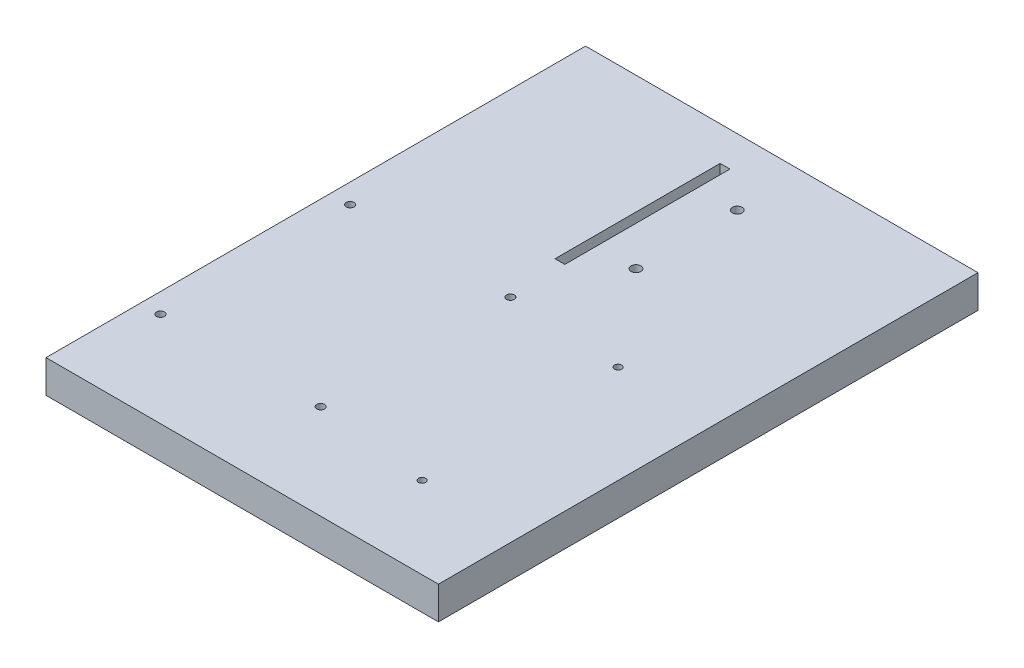
SolidWorks part; units mm, degrees
ref_plane "Front Plane" through (0, 0, 0) normal (0, 0, 1) x (1, 0, 0)
ref_plane "Top Plane" through (0, 0, 0) normal (0, 1, 0) x (1, 0, 0)
ref_plane "Right Plane" through (0, 0, 0) normal (1, 0, 0) x (0, 0, -1)
sketch "Sketch1" plane through (0, 0, 0) normal (0, 1, 0) x (1, 0, 0)
  line L1 (0, 0) -> (120, 0)
  line L2 (0, 0) -> (0, 165)
  line L3 (0, 165) -> (120, 165)
  line L4 (120, 0) -> (120, 165)
  dimension "D1" = 120
  dimension "D2" = 165
extrude "Base" add sketch "Sketch1" along normal blind 10
hole_wizard "Pi-MountHoles" positions "Sketch13" profile "Sketch14" counterbore size "M2" standard "ANSI Metric" end condition up to next
sketch "Sketch13" plane through (0, 0, 0) normal (0, -1, 0) x (-1, 0, 0)
  line L1 (0, 0) -> (-120, 0) construction
  line L2 (0, 165) -> (0, 0) construction
  point P0 (-6, 29)
  point P2 (-55, 29)
  point P4 (-55, 87)
  point P6 (-6, 87)
  dimension "D1" = 49
  dimension "D2" = 58
  dimension "D3" = 87
  dimension "D4" = 6
sketch "Sketch14" plane through (6, 0, -29) normal (1, 0, 0) x (0, 0, -1)
  line L0 (0, 0) -> (0, 10)
  line L1 (0, 10) -> (1.2, 10)
  line L3 (1.2, 10) -> (1.2, 1.6)
  line L4 (2.5, 1.6) -> (1.2, 1.6)
  line L5 (2.5, 1.6) -> (2.5, 0.025)
  line L6 (2.5, 0.025) -> (2.525, 0)
  line L7 (2.525, 0) -> (0, 0)
  line L8 (-2.5, 0.025) -> (-2.525, 0) construction
  line L11 (0, -6.35) -> (0, 107.95) construction
  dimension "Thru Hole Dia." = 2.4
  dimension "Thru Hole Depth" = 10
  dimension "C'Bore Dia." = 5
  dimension "C'Bore Depth" = 1.6
  dimension "Near C'Sink Dia." = 5.05
  dimension "Near C'Sink Angle" = 90
hole_wizard "Battery-MountHoles" positions "Sketch15" profile "Sketch16" counterbore size "M2" standard "ANSI Metric" end condition up to next
sketch "Sketch15" plane through (0, 0, 0) normal (0, -1, 0) x (-1, 0, 0)
  line L0 (0, 0) -> (-120, 0) construction
  circle A0 centre (-55, 87) radius 1.2 construction
  point P0 (-90, 25)
  point P2 (-90, 84.95)
  dimension "D1" = 59.95
  dimension "D2" = 25
  dimension "D3" = 35
sketch "Sketch16" plane through (90, 0, -25) normal (1, 0, 0) x (0, 0, -1)
  line L0 (0, 0) -> (0, 10)
  line L1 (0, 10) -> (1.1, 10)
  line L3 (1.1, 10) -> (1.1, 1.6)
  line L4 (2.5, 1.6) -> (1.1, 1.6)
  line L5 (2.5, 1.6) -> (2.5, 0.025)
  line L6 (2.5, 0.025) -> (2.525, 0)
  line L7 (2.525, 0) -> (0, 0)
  line L8 (-2.5, 0.025) -> (-2.525, 0) construction
  line L11 (0, -6.35) -> (0, 107.95) construction
  dimension "Thru Hole Dia." = 2.2
  dimension "Thru Hole Depth" = 10
  dimension "C'Bore Dia." = 5
  dimension "C'Bore Depth" = 1.6
  dimension "Near C'Sink Dia." = 5.05
  dimension "Near C'Sink Angle" = 90
sketch "Sketch17" plane through (0, 10, 0) normal (0, 1, 0) x (1, 0, 0)
  line L1 (51.65, 154.5) -> (54.65, 154.5)
  line L2 (51.65, 154.5) -> (51.65, 104)
  line L3 (51.65, 104) -> (54.65, 104)
  line L4 (54.65, 154.5) -> (54.65, 104)
  circle A4 centre (55, 87) radius 1.2 construction
  dimension "D1" = 3.35
  dimension "D4" = 17
  dimension "D2" = 3
  dimension "D3" = 50.5
extrude "StepperBracketSlot" cut sketch "Sketch17" against normal up to surface (10 mm away) up to face at (90, 0, -27.525)
sketch "Sketch18" plane through (0, 10, 0) normal (0, 1, 0) x (1, 0, 0)
  line L1 (54.65, 104) -> (54.65, 154.5) construction
  circle A0 centre (66.65, 144.75) radius 1.5
  circle A1 centre (66.65, 113.75) radius 1.5
  point P10 (54.65, 129.25)
  dimension "D1" = 3
  dimension "D2" = 31
  dimension "D3" = 15.5
  dimension "D4" = 12
extrude "AngleBracket-MountHoles" cut sketch "Sketch18" against normal up to surface (10 mm away) up to face at (53.15, 0, -129.25)
equation "\"D3@Sketch18\"=\"D2@Sketch18\"/2"
